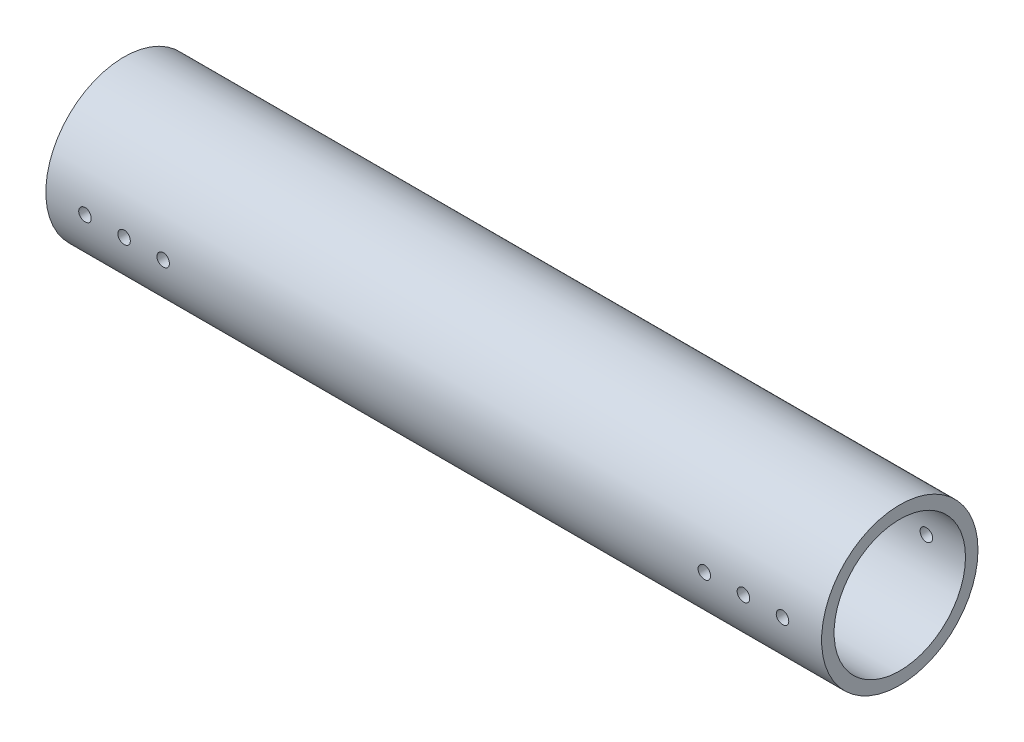
SolidWorks part; units mm, degrees
material "Zoltek Panex 33"
ref_plane "Спереди" through (0, 0, 0) normal (0, 0, 1) x (1, 0, 0)
ref_plane "Сверху" through (0, 0, 0) normal (0, 1, 0) x (1, 0, 0)
ref_plane "Справа" through (0, 0, 0) normal (1, 0, 0) x (0, 0, -1)
other "Configuration Table"
sketch "Эскиз2" plane through (0, 0, 0) normal (1, 0, 0) x (0, 0, -1)
  circle A0 centre (0, 0) radius 25
  circle A1 centre (0, 0) radius 21
  dimension "D1" = 50
  dimension "D2" = 42
extrude "Бобышка-Вытянуть2" add sketch "Эскиз2" along normal blind 248
ref_plane "Плоскость1" through (0, 0, 25) normal (0, 0, 1) x (1, 0, 0)
sketch "Эскиз4" plane through (0, 0, 25) normal (0, 0, 1) x (1, 0, 0)
  line L0 (0, -25) -> (248, -25) construction
  line L1 (248, -25) -> (248, 25) construction
  circle A0 centre (12.5, 0) radius 2
  circle A1 centre (235.5, 0) radius 2
  circle A2 centre (25, 0) radius 2
  circle A3 centre (37.5, 0) radius 2
  circle A4 centre (223, 0) radius 2
  circle A5 centre (210.5, 0) radius 2
  dimension "D1" = 4
  dimension "D4" = 4
  dimension "D6" = 4
  dimension "D8" = 4
  dimension "D10" = 4
  dimension "D11" = 4
  dimension "D2" = 12.5
  dimension "D3" = 25
  dimension "D5" = 12.5
  dimension "D7" = 12.5
  dimension "D9" = 12.5
  dimension "15" = 12.5
  dimension "D12" = 12.5
extrude "Вырез-Вытянуть2" cut sketch "Эскиз4" against normal through all and the other way blind 10 contours A0 | A1 | A2 | A3 | A5 | A4
equation "\"Diameter\"= 50мм"
equation "\"D1@Эскиз2\"= \"Diameter\""
equation "\"Length\" = 248мм"
equation "\"Thickness\"= 4мм"
equation "\"D1@Бобышка-Вытянуть2\"= \"Length\""
equation "\"D2@Эскиз2\" = \"Diameter\" - \"Thickness\" * 2"
equation "\"D4@Эскиз4\"=\"D1@Эскиз4\""
equation "\"D5@Эскиз4\"=\"D2@Эскиз4\""
equation "\"D3@Эскиз4\"=\"Diameter\"/2"
equation "\"D6@Эскиз4\"=\"D1@Эскиз4\""
equation "\"D8@Эскиз4\"=\"D6@Эскиз4\""
equation "\"D10@Эскиз4\"=\"D4@Эскиз4\""
equation "\"D11@Эскиз4\"=\"D4@Эскиз4\""
equation "\"D9@Эскиз4\"=\"D7@Эскиз4\""
